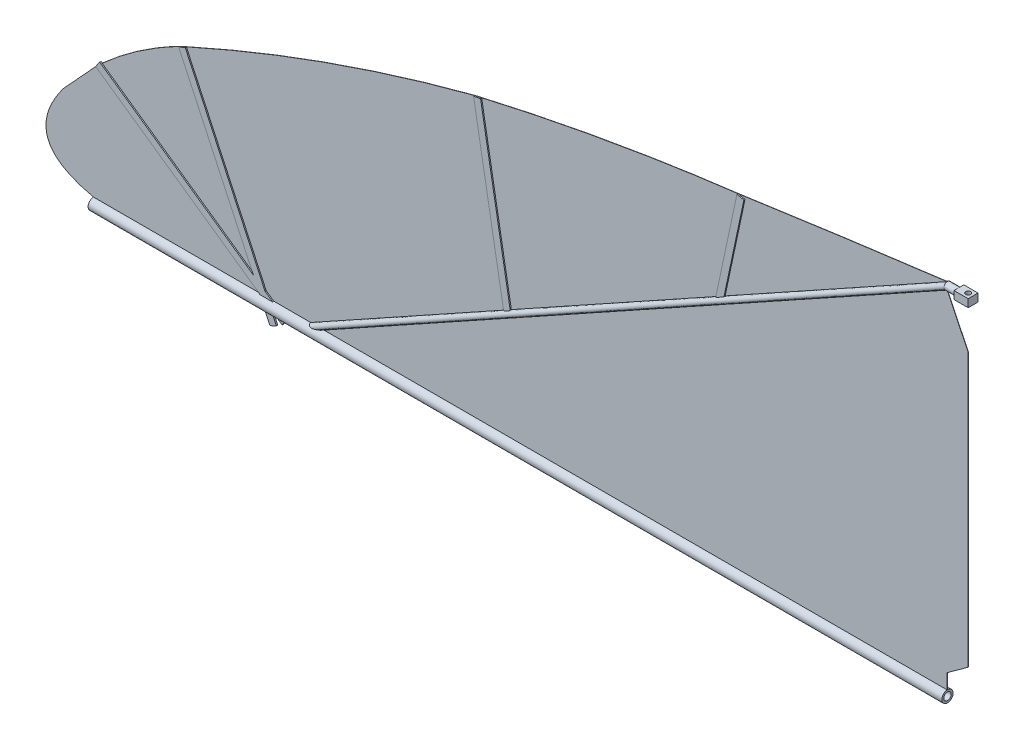
SolidWorks part; units mm, degrees
ref_plane "Front Plane" through (0, 0, 0) normal (0, 0, 1) x (1, 0, 0)
ref_plane "Top Plane" through (0, 0, 0) normal (0, 1, 0) x (1, 0, 0)
ref_plane "Right Plane" through (0, 0, 0) normal (1, 0, 0) x (0, 0, -1)
sketch "Sketch1" plane through (0, 0, 0) normal (0, 0, 1) x (1, 0, 0)
  line L0 (-300, 0) -> (300, 0)
  dimension "D1" = 600
  dimension "D2" = 300
ref_plane "Plane1" through (-300, 0, 0) normal (1, 0, 0) x (0, 0, -1)
sketch "Sketch2" plane through (-300, 0, 0) normal (1, 0, 0) x (0, 0, -1)
  circle A0 centre (0, 0) radius 4
  circle A1 centre (0, 0) radius 2.6
  dimension "D1" = 8
sweep "Sweep1" add profiles "Sketch2" path "Sketch1"
sketch "Sketch3" plane through (0, 0, 0) normal (0, 0, 1) x (1, 0, 0)
  line L0 (-150, 0) -> (300, 250)
  line L1 (-300, -2.75) -> (-300, 2.75) construction
  dimension "D1" = 150
  dimension "D2" = 250
  dimension "D3" = 300
ref_plane "Plane2" through (300, 0, 0) normal (1, 0, 0) x (0, 0, -1)
sketch "Sketch4" plane through (300, 0, 0) normal (1, 0, 0) x (0, 0, -1)
  circle A0 centre (0, 250) radius 2.5
  dimension "D1" = 5
sweep "Sweep2" add profiles "Sketch4" path "Sketch3"
sketch "Sketch5" plane through (0, 0, 0) normal (0, 0, 1) x (1, 0, 0)
  line L0 (-166.6485, -6.7492) -> (-297.7128, 85.0231)
  line L1 (300, 252.5) -> (-147.3, 4) construction
  line L2 (-175.1843, -11.4913) -> (-239.2975, 126)
  line L3 (300, 252.5) -> (-147.3, 4) construction
  line L4 (-10.9285, 79.762) -> (-32.0877, 199.762)
  line L5 (300, 252.5) -> (-147.3, 4) construction
  line L6 (138.1416, 162.5787) -> (153.0206, 232.5787)
  line L7 (300, 252.5) -> (-147.3, 4) construction
  line L8 (-147.3, 4) -> (-300, 4) construction
  line L9 (-300, -4) -> (300, -4) construction
  line L10 (-300, -2.75) -> (-300, 2.75) construction
  line L11 (300, -2.75) -> (300, 2.75) construction
  line L12 (138.1416, 162.5787) -> (300, 252.5)
  line L13 (-166.6485, -6.7492) -> (138.1416, 162.5787)
  line L14 (-166.6485, -6.7492) -> (-147.3, 4)
  line L15 (-147.3, 4) -> (-300, 4)
  line L16 (-166.6485, -6.7492) -> (-175.1843, -11.4913)
  line L17 (-175.1843, -11.4913) -> (-10.9285, 79.762)
  line L18 (-166.6485, -6.7492) -> (-175.1843, -11.4913)
  line L19 (-10.9285, 79.762) -> (138.1416, 162.5787)
  line L20 (-10.9285, 79.762) -> (138.1416, 162.5787)
  line L21 (300, 4) -> (300, 252.5)
  line L22 (300, 4) -> (-138.3, 4) construction
  line L23 (300, 4) -> (300, 247.5)
  line L24 (300, 247.5) -> (-138.3, 4)
  line L25 (-138.3, 4) -> (300, 247.5) construction
  line L26 (300, 4) -> (-138.3, 4) construction
  line L27 (-138.3, 4) -> (300, 4)
  spline S0 degree 2 poles (-300, 4) (-353.4544, 15.6331) (-321.3264, 59.3064) knots 0 0 0 1 1 1
  spline S1 degree 1 poles (-297.7128, 85.0231) (-321.3264, 59.3064) knots 0 0 1 1
  spline S2 degree 2 poles (-297.7128, 85.0231) (-271.3773, 109.6248) (-239.2975, 126) knots 0 0 0 1 1 1
  spline S3 degree 2 poles (-239.2975, 126) (-138.8897, 171.7471) (-32.0877, 199.762) knots 0 0 0 1 1 1
  spline S4 degree 2 poles (-32.0877, 199.762) (59.582, 221.0981) (153.0206, 232.5787) knots 0 0 0 1 1 1
  spline S5 degree 2 poles (153.0206, 232.5787) (226.4208, 243.2011) (300, 252.5) knots 0 0 0 1 1 1
  dimension "D1" = 35
  dimension "D2" = 30
  dimension "D3" = 15
  dimension "D4" = 22
  dimension "D5" = 160
  dimension "D6" = 130
  dimension "D7" = 120
  dimension "D8" = 70
extrude "Boss-Extrude1" add sketch "Sketch5" along normal blind 0.2 separate body contours L0 S1 S0 L15 L14 | S2 L0 L13 L2 | S3 L2 L13 L4 | S4 L4 L13 L6 | S5 L6 L12 region at (-118.7782, 101.289, 0) region at (-274.5206, 33.2445, 0) region at (-240.5934, 72.6682, 0) region at (53.0717, 168.1071, 0) region at (197.2474, 216.0617, 0)
extrude "Extrude-Thin1" add sketch "Sketch5<3>" along normal blind 1 thin contours L0 | L2 | L4 | L6 thin type one direction wall 5
sketch "Sketch5<3>" plane through (0, 0, 0) normal (0, 0, 1) x (1, 0, 0) same geometry as "Sketch5"
sketch "Sketch6" plane through (0, 0, 0) normal (0, 0, 1) x (1, 0, 0)
  line L0 (300, 4) -> (300, 247.5)
  line L1 (300, 4) -> (-138.3, 4) construction
  line L2 (-138.3, 4) -> (300, 247.5) construction
  line L3 (300, 4) -> (-138.3, 4)
  line L4 (-138.3, 4) -> (300, 247.5)
extrude "Boss-Extrude5" add sketch "Sketch6" along normal blind 0.2 separate body
sketch "Sketch8" plane through (0, 0, 0) normal (0, 0, 1) x (1, 0, 0)
  line L0 (300, 247.5) -> (314.6735, 216.9812)
  line L1 (300, 247.5) -> (-138.3, 4) construction
  line L4 (300, 4) -> (300, 247.5) construction
  line L6 (314.6735, 216.9812) -> (314.6735, 25.1507)
  line L7 (314.6735, 25.1507) -> (300, 14.5139)
  line L8 (300, 14.5139) -> (300, 252.5)
extrude "Boss-Extrude8" add sketch "Sketch8" along normal blind 0.2 contours L8 L7 L6 L0 region at (307.0998, 126.1969, 0)
ref_plane "Plane3" through (400, 0, 0) normal (1, 0, 0) x (0, 0, -1)
sketch "Sketch10" plane through (300, 0, 0) normal (1, 0, 0) x (0, 0, -1)
  circle A0 centre (0, 250) radius 2.5
  dimension "D1" = 5
extrude "Boss-Extrude13" add sketch "Sketch10" along normal blind 8
sketch "Sketch11" plane through (308, 0, 0) normal (1, 0, 0) x (0, 0, -1)
  line L1 (-3.4547, 252.7631) -> (3.4547, 252.7631)
  line L2 (-3.4547, 252.7631) -> (-3.4547, 247.2369)
  line L3 (-3.4547, 247.2369) -> (3.4547, 247.2369)
  line L4 (3.4547, 252.7631) -> (3.4547, 247.2369)
  line L5 (-3.4547, 252.7631) -> (3.4547, 247.2369) construction
  line L6 (-3.4547, 247.2369) -> (3.4547, 252.7631) construction
  point P0 (0, 250)
extrude "Boss-Extrude14" add sketch "Sketch11" along normal blind 10
sketch "Sketch12" plane through (0, 252.7631, 0) normal (0, 1, 0) x (1, 0, 0)
  line L0 (318, 3.4547) -> (318, -3.4547) construction
  circle A0 centre (314.5, 0) radius 2
  dimension "D1" = 4
  dimension "D2" = 3.5
sketch "Sketch13" plane through (0, 252.7631, 0) normal (0, 1, 0) x (1, 0, 0)
  circle A0 centre (314.5, 0) radius 1.7434
extrude "Cut-Extrude1" cut sketch "Sketch13" against normal blind 7
